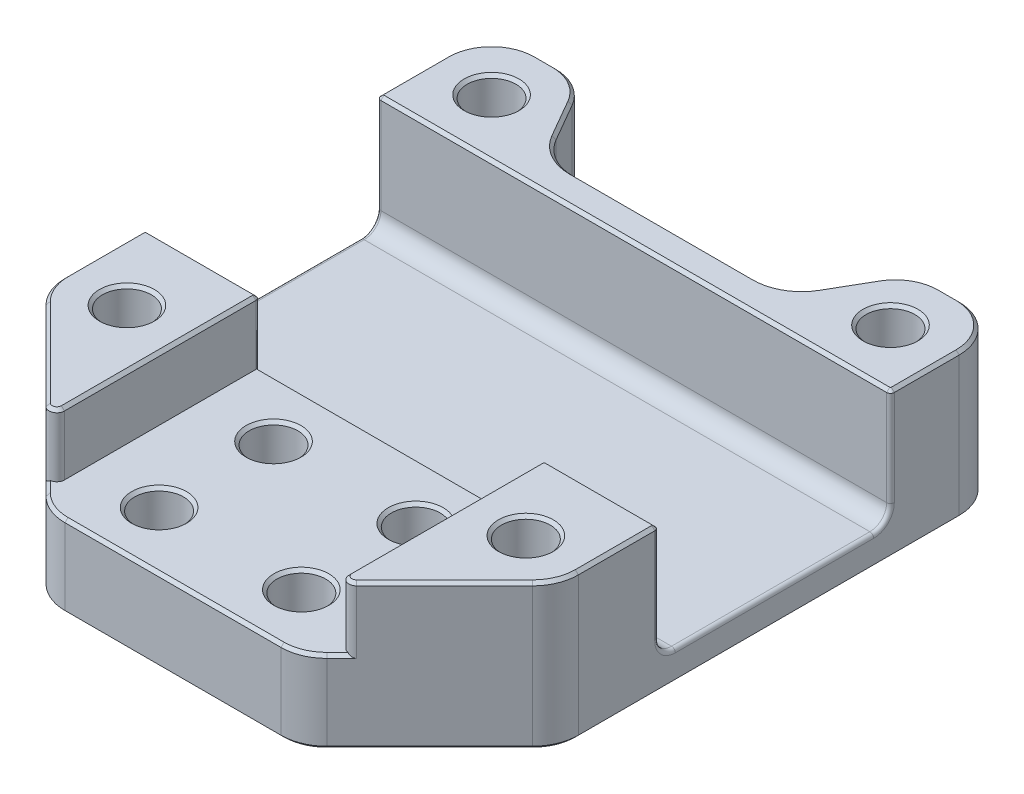
SolidWorks part; units mm, degrees
ref_plane "Front Plane" through (0, 0, 0) normal (1, 0, 0) x (0, 1, 0)
ref_plane "Top Plane" through (0, 0, 0) normal (0, 0, 1) x (0, 1, 0)
ref_plane "Right Plane" through (0, 0, 0) normal (0, 1, 0) x (-1, 0, 0)
sketch "Sketch1" plane through (0, 0, 0) normal (0, 0, 1) x (0, 1, 0)
  line L1 (-8.3312, -18.6436) -> (8.3312, -18.6436)
  line L2 (-8.3312, -18.6436) -> (-8.3312, 18.6436)
  line L3 (-8.3312, 18.6436) -> (8.3312, 18.6436)
  line L4 (8.3312, -18.6436) -> (8.3312, 18.6436)
  line L5 (-8.3312, -18.6436) -> (8.3312, 18.6436) construction
  line L6 (-8.3312, 18.6436) -> (8.3312, -18.6436) construction
  point P0 (0, 0)
  dimension "D1" = 16.6624
  dimension "D2" = 37.2872
extrude "Boss-Extrude1" add sketch "Sketch1" along normal mid plane 200
sketch "Sketch2" plane through (18.6436, 0, 0) normal (1, 0, 0) x (0, 1, 0)
  line L0 (-8.3312, -70.1) -> (-8.3312, -100.1)
  line L1 (-8.3312, -100.1) -> (-15.2, -100.1)
  line L2 (-15.2, -100.1) -> (-15.2, -130.5)
  line L3 (-15.2, -130.5) -> (-0.1, -130.5)
  line L4 (-8.3312, -100) -> (8.3312, -100)
  line L5 (8.3312, -100) -> (8.3312, 100)
  line L6 (8.3312, 100) -> (-8.3312, 100)
  line L7 (-8.3312, 100) -> (-8.3312, -100)
  line L8 (-8.3312, -100) -> (8.3312, -100)
  line L9 (8.3312, -100) -> (8.3312, 100)
  line L10 (8.3312, 100) -> (-8.3312, 100)
  line L11 (-8.3312, 100) -> (-8.3312, -100)
  line L12 (-0.1, -130.5) -> (-0.1, -145.5)
  line L13 (-0.1, -145.5) -> (-19.1, -145.5)
  line L14 (-19.1, -145.5) -> (-19.1, -70.1)
  line L15 (-19.1, -70.1) -> (-8.3312, -70.1)
  line L16 (0, -100) -> (0, -140.2396)
  line L17 (-0.1, -130.5) -> (-0.1, -70.1)
  line L18 (-0.1, -70.1) -> (-8.3312, -70.1)
  line L19 (-8.3312, -100.1) -> (0, -100.1)
  line M14 (-8.3312, -100) -> (8.3312, -100)
  line M17 (-8.3312, 100) -> (-8.3312, -100)
  dimension "D2" = 30.4
  dimension "D3" = 0.1
  dimension "D4" = 0.1
  dimension "D5" = 15.2
  dimension "D6" = 3.9
  dimension "D7" = 15
  dimension "D8" = 30
  dimension "D1" = 0
ref_plane "Plane1" through (0, 0, 0) normal (1, 0, 0) x (0, 0, -1)
extrude "Boss-Extrude2" add sketch "Sketch2" against normal up to surface (18.6436 mm away) separate body contours L15 L14 L13 L12 L3 L2 L1 L0 M17 region at (18.6436, -9.1088, -85.05) up to plane "Plane1"
extrude "Boss-Extrude3" add sketch "Sketch2<3>" along normal blind 15 contours L15 L14 L13 L12 L3 L2 L1 L0 M17 | L17 L18 M17 M14 | L0 L19 L17 M14 region at (18.6436, -4.2156, -85.05) region at (18.6436, -9.1088, -85.05) region at (18.6436, -4.2156, -100.05)
sketch "Sketch2<3>" plane through (18.6436, 0, 0) normal (1, 0, 0) x (0, 1, 0) same geometry as "Sketch2"
ref_plane "Plane2" through (0, 0, 0) normal (0, 1, 0) x (1, 0, 0)
delete or keep bodies "Body-Delete/Keep 1" type delete bodies bodies 101
sketch "Sketch3" plane through (0, -19.1, 0) normal (0, -1, 0) x (1, 0, 0)
  line L0 (0, -70.1) -> (33.6436, -70.1) construction
  line L1 (33.6436, -145.5) -> (33.6436, -70.1) construction
  line L2 (0, -70.1) -> (33.6436, -70.1)
  line L3 (33.6436, -145.5) -> (33.6436, -70.1)
  line L4 (0, -145.5) -> (33.6436, -145.5) construction
  line L5 (0, -145.5) -> (33.6436, -145.5)
  line L6 (0, -130.5) -> (33.6436, -130.5) construction
  line L7 (0, -130.5) -> (33.6436, -130.5)
  line L8 (18.6436, -70.1) -> (18.6436, -100.1) construction
  line L9 (0, -100.1) -> (33.6436, -100.1) construction
  line L10 (18.6436, -70.1) -> (18.6436, -100.1)
  line L11 (0, -100.1) -> (33.6436, -100.1)
  line L12 (9.3218, -77.6) -> (9.3218, -70.1) construction
  line L13 (0, -55) -> (0, 55) construction
  line L14 (26.1436, -90.2066) -> (26.1436, -70.1) construction
  line L15 (16.6436, -70.1) -> (33.6436, -87.1)
  line L16 (26.1436, -90.2066) -> (33.6436, -87.1) construction
  line L17 (26.1436, -138) -> (33.6436, -138) construction
  line L18 (0, -134.5) -> (15.4626, -134.5)
  line L19 (0, -70.1) -> (0, -145.5) construction
  line L20 (15.4626, -134.5) -> (21.8135, -145.5)
  line L21 (26.1436, -138) -> (21.8135, -145.5) construction
  circle A0 centre (9.3218, -92.6) radius 3.2
  circle A1 centre (9.3218, -92.6) radius 5.2 construction
  circle A2 centre (9.3218, -77.6) radius 3.2
  circle A3 centre (9.3218, -77.6) radius 5.2 construction
  circle A4 centre (26.1436, -90.2066) radius 3.2
  circle A5 centre (26.1436, -138) radius 3.2
  line M21 (33.6436, -70.1) -> (0, -70.1)
  line M22 (0, -70.1) -> (0, -145.5)
  line M23 (0, -145.5) -> (33.6436, -145.5)
  dimension "D1" = 6.4
  dimension "D2" = 10.4
  dimension "D3" = 18.6436
  dimension "D4" = 9.3218
  dimension "D5" = 30
  dimension "D6" = 7.5
  dimension "D7" = 7.5
  dimension "D8" = 15
  dimension "D9" = 7.5
  dimension "D10" = 2
  dimension "D11" = 45
  dimension "D12" = 67.5
  dimension "D13" = 15
  dimension "D14" = 7.5
  dimension "D15" = 120
  dimension "D16" = 4
  dimension "D17" = 60
extrude "Cut-Extrude1" cut sketch "Sketch3" against normal through all contours L20 L18 M22 M23 | A5 | A4 | L10 L15 L3 M21 | L2 L15 L10 | A2 | A0 region at (17.9769, -19.1, -70.7667) region at (28.1173, -19.1, -75.8368) region at (9.4092, -19.1, -140.3124) region at (9.3218, -19.1, -92.6) region at (9.3218, -19.1, -77.6) region at (26.1436, -19.1, -90.2066) region at (26.1436, -19.1, -138)
fillet "Fillet1" radius 6 5 edges at (16.6436, -13.7156, -70.1) (33.6436, -9.6, -145.5) (21.8135, -9.6, -145.5) (15.4626, -9.6, -134.5) (33.6436, -9.6, -87.1)
fillet "Fillet3" radius 2.2 2 edges at (16.8218, -15.2, -130.5) (16.8218, -15.2, -100.1)
fillet "Fillet2" radius 0.5 6 edges at (33.6436, -6.55, -130.5) (18.6436, -4.2156, -100.1) (33.6436, -6.55, -100.1) (33.6436, -14.5556, -129.8556) (33.6436, -15.2, -115.3) (33.6436, -14.5556, -100.7444)
fillet "Fillet4" radius 1 1 edges at (18.6436, -4.2156, -72.1)
chamfer "Chamfer1" distance 0.4 angle 45 40 edges at (9.3218, -8.3312, -95.8) (9.3218, -19.1, -95.8) (9.3218, -8.3312, -80.8) (9.3218, -19.1, -80.8) (26.1436, -19.1, -93.4066) (26.1436, -0.1, -93.4066) (26.1436, -19.1, -141.2) (26.1436, -0.1, -141.2) (9.5718, -8.3312, -100.1) (19.3758, -8.3312, -72.8322) (16.4544, -8.3312, -70.5567) (7.0792, -8.3312, -70.1) (5.9993, -0.1, -134.5) (14.9985, -0.1, -135.3038) (18.638, -0.1, -140) (22.2776, -0.1, -144.6962) (16.5718, -0.1, -130.5) (26.4606, -0.1, -145.5) (33.4972, -0.1, -130.6464) (31.8862, -0.1, -143.7426) (33.6436, -0.1, -135.25) (33.6436, -0.1, -94.5926) (33.4972, -0.1, -99.9536) (33.1869, -0.1, -87.2892) (26.1436, -0.1, -100.1) (26.1185, -0.1, -79.5749) (18.79, -0.1, -99.9536) (18.6436, -0.1, -87.0571) (5.9993, -19.1, -134.5) (14.9985, -19.1, -135.3038) (18.638, -19.1, -140) (7.0792, -19.1, -70.1) (22.2776, -19.1, -144.6962) (16.4544, -19.1, -70.5567) (26.4606, -19.1, -145.5) (25.1436, -19.1, -78.6) (31.8862, -19.1, -143.7426) (33.1869, -19.1, -87.2892) (33.6436, -19.1, -114.5426) (19.2609, -0.1, -73.5903)
mirror "Mirror1" about plane through (0, 0, 0) normal (1, 0, 0) of bodies 104
equation "\"D4@Sketch3\"=\"D3@Sketch3\"/2"
equation "\"D6@Sketch3\"=\"D5@Sketch3\"/4"
equation "\"D7@Sketch3\"=\"D6@Sketch3\""
equation "\"D9@Sketch3\"=\"D8@Sketch3\"/2"
equation "\"D12@Sketch3\"=(180deg-\"D11@Sketch3\")/2"
equation "\"D14@Sketch3\"=\"D13@Sketch3\"/2"
equation "\"D17@Sketch3\"=\"D15@Sketch3\"/2"
